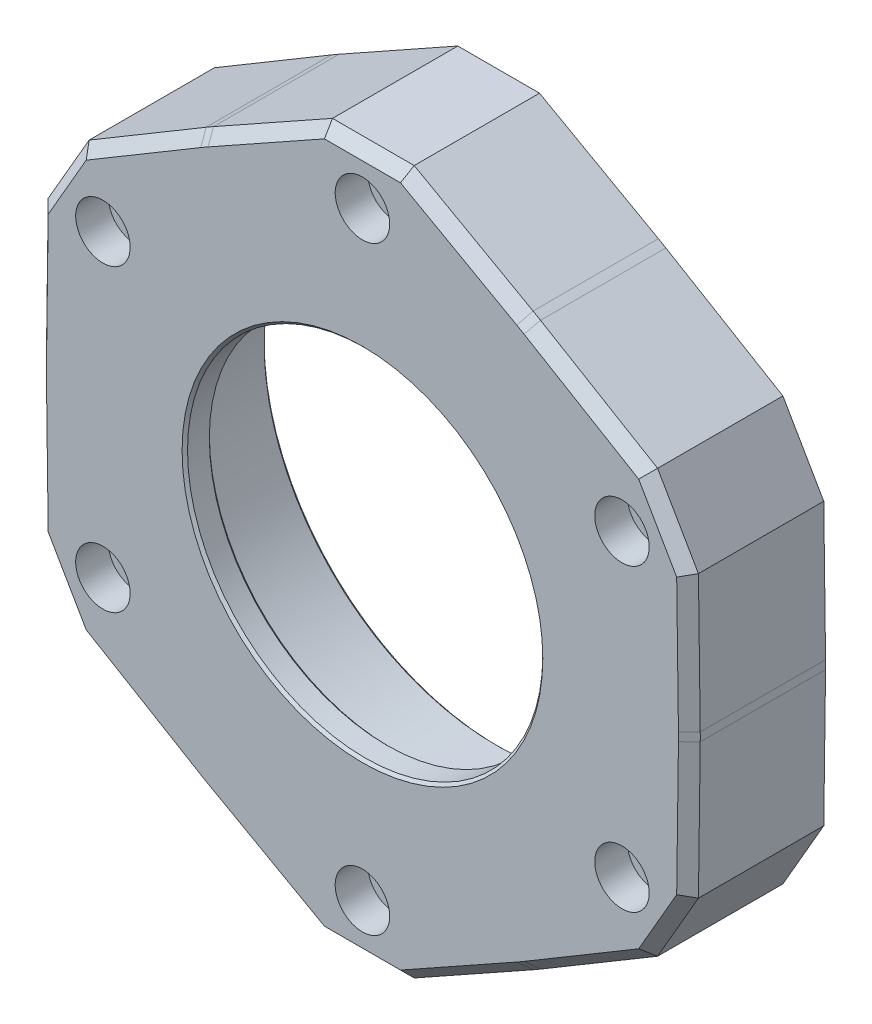
SolidWorks part; units mm, degrees
ref_plane "Front Plane" through (0, 0, 0) normal (0, 0, 1) x (1, 0, 0)
ref_plane "Top Plane" through (0, 0, 0) normal (0, 1, 0) x (1, 0, 0)
ref_plane "Right Plane" through (0, 0, 0) normal (1, 0, 0) x (0, 0, -1)
sketch "Sketch1" plane through (0, 0, 0) normal (0, 0, 1) x (1, 0, 0)
  circle A0 centre (0, 0) radius 60
  circle A1 centre (0, 0) radius 55 construction
  circle A2 centre (0, 55) radius 2.55
  circle A3 centre (47.6314, 27.5) radius 2.55
  circle A4 centre (47.6314, -27.5) radius 2.55
  circle A5 centre (0, -55) radius 2.55
  circle A6 centre (-47.6314, -27.5) radius 2.55
  circle A7 centre (-47.6314, 27.5) radius 2.55
  circle A8 centre (0, 0) radius 42.55
  point P18 (0, 0)
  dimension "D1" = 120
  dimension "D2" = 110
  dimension "D3" = 5.1
  dimension "D5" = 85.1
  dimension "D4" = 6
extrude "Boss-Extrude1" add sketch "Sketch1" along normal blind 25
sketch "Sketch3" plane through (0, 0, 25) normal (0, 0, 1) x (1, 0, 0)
  circle A0 centre (0, 0) radius 42.55
  circle A1 centre (0, 0) radius 32.6
  dimension "D1" = 85.1
  dimension "D2" = 65.2
extrude "Boss-Extrude2" add sketch "Sketch3" against normal blind 5
sketch "Sketch7" plane through (0, 0, 0) normal (0, 0, -1) x (-1, 0, 0)
  line L0 (-29.3133, 52.352) -> (-7.5, 64.5659)
  line L1 (-7.5, 64.5659) -> (7.5, 64.5659)
  line L2 (7.5, 64.5659) -> (29.3133, 52.352)
  line L3 (59.6657, 25.7877) -> (59.9948, 0.7899)
  line L4 (52.1657, 38.7781) -> (59.6657, 25.7877)
  line L5 (30.6815, 51.5621) -> (52.1657, 38.7781)
  line L6 (52.1657, -38.7781) -> (30.6815, -51.5621)
  line L7 (59.6657, -25.7877) -> (52.1657, -38.7781)
  line L8 (59.9948, -0.7899) -> (59.6657, -25.7877)
  line L9 (-7.5, -64.5659) -> (-29.3133, -52.352)
  line L10 (7.5, -64.5659) -> (-7.5, -64.5659)
  line L11 (29.3133, -52.352) -> (7.5, -64.5659)
  line L12 (-59.6657, -25.7877) -> (-59.9948, -0.7899)
  line L13 (-52.1657, -38.7781) -> (-59.6657, -25.7877)
  line L14 (-30.6815, -51.5621) -> (-52.1657, -38.7781)
  line L15 (-52.1657, 38.7781) -> (-30.6815, 51.5621)
  line L16 (-59.6657, 25.7877) -> (-52.1657, 38.7781)
  line L17 (-59.9948, 0.7899) -> (-59.6657, 25.7877)
  circle A0 centre (0, 0) radius 65 construction
  circle A1 centre (0, 0) radius 60 construction
  arc A2 (-30.6815, 51.5621) -> (-59.9948, 0.7899) centre (0, 0) ccw
  arc A3 (29.3133, 52.352) -> (-29.3133, 52.352) centre (0, 0) ccw
  arc A4 (59.9948, 0.7899) -> (30.6815, 51.5621) centre (0, 0) ccw
  arc A5 (30.6815, -51.5621) -> (59.9948, -0.7899) centre (0, 0) ccw
  arc A6 (-29.3133, -52.352) -> (29.3133, -52.352) centre (0, 0) ccw
  arc A7 (-59.9948, -0.7899) -> (-30.6815, -51.5621) centre (0, 0) ccw
  point P8 (0, 64.5659)
  point P35 (0, 0)
  dimension "D1" = 130
  dimension "D2" = 15
  dimension "D3" = 6
extrude "Boss-Extrude3" add sketch "Sketch7" against normal up to surface (25 mm away) up to face at (-45.0814, -27.5, 25)
sketch "Sketch8" plane through (0, 0, 25) normal (0, 0, 1) x (1, 0, 0)
  circle A0 centre (0, 55) radius 5
  circle A1 centre (47.6314, 27.5) radius 5
  circle A2 centre (47.6314, -27.5) radius 5
  circle A3 centre (0, -55) radius 5
  circle A4 centre (-47.6314, -27.5) radius 5
  circle A5 centre (-47.6314, 27.5) radius 5
  point P15 (0, 0)
  dimension "D1" = 10
  dimension "D2" = 6
extrude "Cut-Extrude1" cut sketch "Sketch8" against normal blind 6
chamfer "Chamfer2" distance 0.5 angle 45 3 edges at (42.55, 0, 0) (32.6, 0, 20) (32.6, 0, 25)
chamfer "Chamfer3" distance 2 angle 45 24 edges at (-18.4067, 58.4589, 25) (0, 64.5659, 25) (18.4067, 58.4589, 25) (30, 51.9615, 25) (41.4236, 45.1701, 25) (55.9157, 32.2829, 25) (59.8302, 13.2888, 25) (60, 0, 25) (59.8302, -13.2888, 25) (55.9157, -32.2829, 25) (41.4236, -45.1701, 25) (30, -51.9615, 25) (18.4067, -58.4589, 25) (0, -64.5659, 25) (-18.4067, -58.4589, 25) (-30, -51.9615, 25) (-41.4236, -45.1701, 25) (-55.9157, -32.2829, 25) (-59.8302, -13.2888, 25) (-60, 0, 25) (-59.8302, 13.2888, 25) (-55.9157, 32.2829, 25) (-41.4236, 45.1701, 25) (-30, 51.9615, 25)
sketch "Sketch9" plane through (0, 0, 0) normal (0, 0, -1) x (-1, 0, 0)
  line L0 (0, 48) -> (0, 0) construction
  line L1 (0, 0) -> (-8.3351, 47.2708) construction
  circle A55 centre (0, 0) radius 48 construction
  circle A56 centre (-8.3351, 47.2708) radius 4.075
  circle A57 centre (8.3351, 47.2708) radius 4.075
  circle A58 centre (24, 41.5692) radius 4.075
  circle A59 centre (36.7701, 30.8538) radius 4.075
  circle A60 centre (45.1052, 16.417) radius 4.075
  circle A61 centre (48, 0) radius 4.075
  circle A62 centre (45.1052, -16.417) radius 4.075
  circle A63 centre (36.7701, -30.8538) radius 4.075
  circle A64 centre (24, -41.5692) radius 4.075
  circle A65 centre (8.3351, -47.2708) radius 4.075
  circle A66 centre (-8.3351, -47.2708) radius 4.075
  circle A67 centre (-24, -41.5692) radius 4.075
  circle A68 centre (-36.7701, -30.8538) radius 4.075
  circle A69 centre (-45.1052, -16.417) radius 4.075
  circle A70 centre (-48, 0) radius 4.075
  circle A71 centre (-45.1052, 16.417) radius 4.075
  circle A72 centre (-36.7701, 30.8538) radius 4.075
  circle A73 centre (-24, 41.5692) radius 4.075
  point P42 (0, 0)
  point P61 (0, 0)
  point P96 (0, 0)
  dimension "D1" = 96
  dimension "D3" = 8.15
  dimension "D4" = 18
  dimension "D2" = 10
extrude "Cut-Extrude2" cut sketch "Sketch9" against normal blind 7
